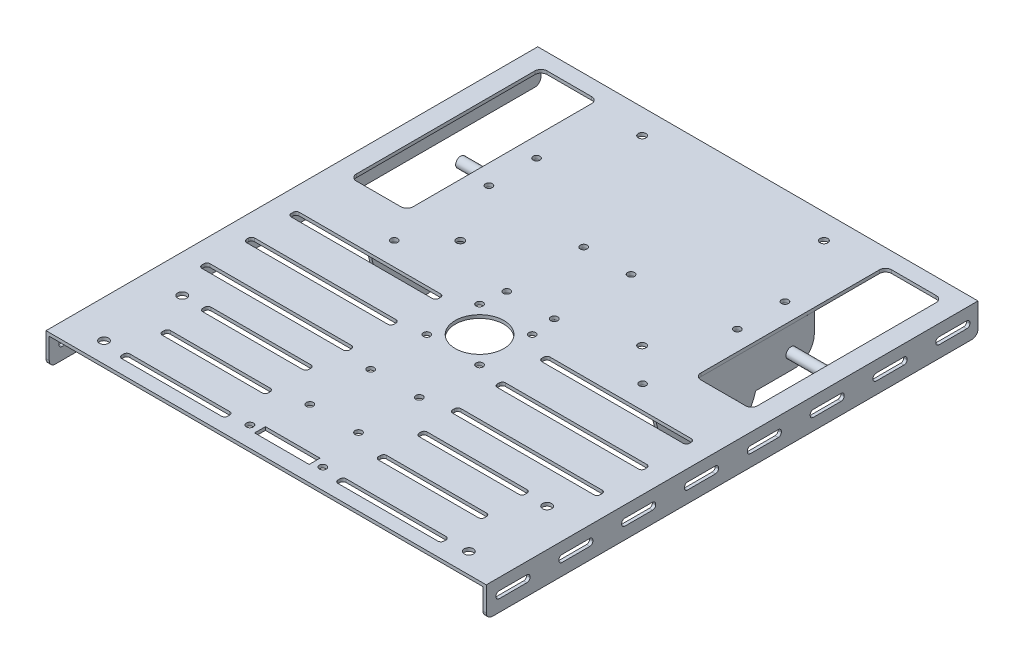
SolidWorks part; units mm, degrees
ref_plane "Front Plane" through (0, 0, 0) normal (0, 0, 1) x (1, 0, 0)
ref_plane "Top Plane" through (0, 0, 0) normal (0, 1, 0) x (1, 0, 0)
ref_plane "Right Plane" through (0, 0, 0) normal (1, 0, 0) x (0, 0, -1)
sketch "Sketch2" plane through (0, 0, 0) normal (0, 1, 0) x (1, 0, 0)
  line L7 (-172.2662, -88.2141) -> (41.7338, -88.2141)
  line L48 (-164.2662, 146.3841) -> (-136.2662, 146.3841)
  line L49 (-164.2662, 146.3841) -> (-164.2662, 52.2603)
  line L50 (-164.2662, 52.2603) -> (-136.2662, 52.2603)
  line L51 (-136.2662, 146.3841) -> (-136.2662, 52.2603)
  line L72 (41.7338, 154.3841) -> (-172.2662, 154.3841)
  line L75 (-65.2662, 154.3841) -> (-65.2662, -88.2141) construction
  line L76 (41.7338, -88.2141) -> (41.7338, 154.3841)
  line L77 (5.7338, 146.3841) -> (5.7338, 52.2603)
  line L78 (33.7338, 52.2603) -> (5.7338, 52.2603)
  line L79 (-172.2662, -88.2141) -> (-172.2662, 154.3841)
  line L80 (33.7338, 146.3841) -> (33.7338, 52.2603)
  line L81 (33.7338, 146.3841) -> (5.7338, 146.3841)
  point P2 (-150.2662, 146.3841)
  dimension "D1" = 8
  dimension "D3" = 8
  dimension "D6" = 107
  dimension "D9" = 28
extrude "Boss-Extrude1" add sketch "Sketch2" along normal blind 1.6
ref_plane "Plane3" through (-65.2662, 0, 0) normal (-1, 0, 0) x (0, 0, 1)
sketch "Sketch4" plane through (0, 0, 0) normal (0, -1, 0) x (1, 0, 0)
  line L5 (-172.2662, 15.9553) -> (41.7338, 15.9553) construction
  line L6 (-172.2662, -154.3841) -> (-172.2662, 88.2141) construction
  line L7 (41.7338, 88.2141) -> (41.7338, -154.3841) construction
  point P6 (-65.2662, 15.9553)
  line B0 (-136.2673, -111.2297) -> (-136.2673, -31.6718)
  line B1 (-136.2673, -111.2297) -> (-123.4267, -111.2297)
  line B2 (-136.2673, -31.6718) -> (-123.4299, -31.6718)
  line B3 (-72.7662, -37.9313) -> (-72.7662, -84.2325)
  line B4 (-72.7662, -37.9313) -> (-81.1807, -37.9313)
  line B5 (-72.7662, -84.2325) -> (-81.1807, -84.2325)
  line B6 (-118.4299, -36.6718) -> (-118.4299, -60.4336)
  line B7 (-118.4299, -60.4336) -> (-81.1807, -60.4336)
  line B8 (-81.1807, -60.4336) -> (-81.1807, -37.9313)
  line B9 (-81.1807, -84.2325) -> (-81.1807, -67.1203)
  line B10 (-81.1807, -67.1203) -> (-118.4267, -67.1203)
  line B11 (-118.4267, -67.1203) -> (-118.4267, -106.2297)
  arc B12 (-123.4299, -31.6718) -> (-118.4299, -36.6718) centre (-123.4299, -36.6718) cw
  arc B13 (-123.4267, -111.2297) -> (-118.4267, -106.2297) centre (-123.4267, -106.2297) ccw
  dimension "D1" = 7.5
sketch_block_instance "Block1-1"
sketch_block "Block1" parameters "D1"=5
extrude "Boss-Extrude3" add sketch "Sketch4" along normal blind 1.6129 separate body
sketch "Sketch6" plane through (-136.2673, 113.8349, 0) normal (1, 0, 0) x (0, -1, 0)
  line L1 (113.8349, 31.6718) -> (113.8349, 111.2297)
  line L7 (123.4041, 111.2297) -> (113.8349, 111.2297)
  line L8 (113.8349, 52.2603) -> (113.8349, 146.3841) construction
  line L10 (115.4478, 111.2297) -> (113.8349, 111.2297) construction
  line L11 (133.4041, 101.2297) -> (133.4041, 82.2567)
  line L13 (132.4365, 35.6062) -> (115.4478, 31.6718)
  line L14 (115.4478, 31.6718) -> (113.8349, 31.6718)
  circle A2 centre (133.4041, 71.8386) radius 1.27
  circle A4 centre (133.4041, 49.6644) radius 3
  circle A5 centre (125.8349, 99.7882) radius 2.55
  circle A6 centre (123.1933, 49.6644) radius 1.27
  circle A8 centre (143.6149, 49.6644) radius 1.27
  arc A10 (133.4041, 82.2567) -> (132.4365, 35.6062) centre (127.5185, 59.0435) cw
  arc A11 (133.4041, 101.2297) -> (123.4041, 111.2297) centre (123.4041, 101.2297) ccw
  line M25 (113.8349, 31.6718) -> (113.8349, 111.2297)
  line M26 (113.8349, 111.2297) -> (115.4478, 111.2297)
  line M27 (115.4478, 111.2297) -> (115.4478, 31.6718)
  line M28 (115.4478, 31.6718) -> (113.8349, 31.6718)
  dimension "D1" = 5.1
  dimension "D4" = 6
  dimension "D5" = 10
  dimension "D2" = 12
extrude "Boss-Extrude4" add sketch "Sketch6" along normal blind 1.6129 contours M28 M25 M26 M27 | M27 | A6 A2 A4 A8 region at (-136.2673, -0.8064, -71.4508) region at (-136.2673, -15.5641, -67.9069)
sketch "Sketch7" plane through (0, 0, 0) normal (0, -1, 0) x (1, 0, 0)
  line L0 (-172.2662, 88.2141) -> (41.7338, 88.2141) construction
  line L1 (-65.2662, -5.0799) -> (-65.2662, -29.0799)
  line L48 (-65.2662, -1159.7859) -> (-65.2662, 48840.2141) construction
  line L49 (41.7338, -154.3841) -> (-172.2662, -154.3841) construction
  line L50 (-65.2662, 80.4578) -> (-65.2662, 75.1009)
  line L51 (-65.2662, 80.4578) -> (-78.7298, 80.4578)
  line L52 (-65.2662, 75.1009) -> (-78.7298, 75.1009)
  line L53 (-78.7298, 80.4578) -> (-78.7298, 75.1009)
  circle A0 centre (-126.5406, -82.9719) radius 1.7
  circle A1 centre (-126.5406, -36.2597) radius 1.7
  circle A2 centre (-76.9734, -42.2194) radius 1.7
  circle A3 centre (-76.9734, -80.1262) radius 1.7
  circle A4 centre (-126.5406, -106.4792) radius 1.7
  circle A5 centre (-110.1162, -52.4299) radius 1.9
  circle A6 centre (-110.1162, -142.1299) radius 1.9
  circle A7 centre (-155.2662, 39.5701) radius 2.25
  circle A8 centre (-78.2662, -4.0799) radius 1.7
  circle A9 centre (-78.2662, -30.0799) radius 1.7
  arc A11 (-65.2662, -5.0799) -> (-65.2662, -29.0799) centre (-65.2662, -17.0799) ccw
  circle A12 centre (-83.2662, 78.2141) radius 1.7
  circle A13 centre (-77.2662, 24.6349) radius 1.7
  circle A14 centre (-77.2662, 54.6349) radius 1.7
  circle A15 centre (-155.2662, 78.2141) radius 2.25
  point P38 (-65.2662, -154.3841)
  dimension "D3" = 3.4
  dimension "D4" = 3.4
  dimension "D5" = 3.4
  dimension "D6" = 3.4
  dimension "D1" = 3.4
  dimension "D2" = 3.8
  dimension "D8" = 3.8
  dimension "D9" = 4.5
  dimension "D12" = 3.4
  dimension "D13" = 3.4
  dimension "D14" = 12
  dimension "D20" = 3.4
  dimension "D23" = 3.4
  dimension "D24" = 3.4
  dimension "D22" = 10
  dimension "D25" = 30
  dimension "D15" = 13
  dimension "D19" = 12
  dimension "D21" = 18
  dimension "D11" = 89.7
  dimension "D17" = 13
  dimension "D18" = 26
  dimension "D7" = 92
  dimension "D16" = 44.85
  dimension "D10" = 90
  dimension "D28" = 35.35
extrude "Cut-Extrude1" cut sketch "Sketch7" against normal blind 10 and the other way blind 10
mirror "Mirror1" about plane through (-65.2662, 0, 0) normal (-1, 0, 0) of bodies 157 158 103
mirror "Mirror2" about plane through (-65.2662, 0, 0) normal (-1, 0, 0) of "Cut-Extrude1"
sketch "Sketch9" plane through (-136.2662, 0, 0) normal (1, 0, 0) x (0, 0, -1)
  circle A0 centre (99.7882, -12) radius 2.5
extrude "Boss-Extrude6" add sketch "Sketch9" along normal blind 169 and the other way blind 21 separate body
sketch "Sketch11" plane through (0, 1.6, 0) normal (0, 1, 0) x (1, 0, 0)
  line L0 (-172.2662, 154.3841) -> (-172.2662, -88.2141)
  line L1 (-172.2662, 154.3841) -> (-173.8662, 154.3841)
  line L2 (-172.2662, -88.2141) -> (-173.8662, -88.2141)
  line L3 (-173.8662, 154.3841) -> (-173.8662, -88.2141)
  line L4 (41.7338, 154.3841) -> (41.7338, -88.2141)
  line L5 (41.7338, 154.3841) -> (43.3338, 154.3841)
  line L6 (41.7338, -88.2141) -> (43.3338, -88.2141)
  line L7 (43.3338, 154.3841) -> (43.3338, -88.2141)
  dimension "D1" = 1.6
  dimension "D2" = 1.6
extrude "Boss-Extrude7" add sketch "Sketch11" against normal blind 15
sketch "Sketch12" plane through (0, 1.6, 0) normal (0, 1, 0) x (1, 0, 0)
  line L12 (-65.2662, -1088.2141) -> (-65.2662, 48911.7859) construction
  line L13 (-173.8662, -88.2141) -> (43.3338, -88.2141) construction
  line L78 (-161.9933, 24.8362) -> (-92.2703, 24.8362)
  line L79 (-163.4933, 23.3362) -> (-163.4933, 22.3362)
  line L80 (-90.7703, 23.3362) -> (-90.7703, 22.3362)
  line L81 (-161.9933, 20.8362) -> (-92.2703, 20.8362)
  line L98 (-143.2458, -37.4749) -> (-93.977, -37.4749)
  line L99 (-144.7458, -38.9749) -> (-144.7458, -39.9749)
  line L100 (-92.477, -38.9749) -> (-92.477, -39.9749)
  line L101 (-143.2458, -41.4749) -> (-93.977, -41.4749)
  line L134 (-161.9933, -1.1638) -> (-92.2703, -1.1638)
  line L135 (-90.7703, 1.3362) -> (-90.7703, 0.3362)
  line L136 (-161.9933, 2.8362) -> (-92.2703, 2.8362)
  line L137 (-163.4933, 1.3362) -> (-163.4933, 0.3362)
  line L138 (-161.9933, -23.1638) -> (-92.2703, -23.1638)
  line L139 (-90.7703, -20.6638) -> (-90.7703, -21.6638)
  line L140 (-161.9933, -19.1638) -> (-92.2703, -19.1638)
  line L141 (-163.4933, -20.6638) -> (-163.4933, -21.6638)
  line L142 (-143.2458, -57.4749) -> (-93.977, -57.4749)
  line L143 (-144.7458, -58.9749) -> (-144.7458, -59.9749)
  line L144 (-92.477, -58.9749) -> (-92.477, -59.9749)
  line L145 (-143.2458, -61.4749) -> (-93.977, -61.4749)
  line L146 (-143.2458, -77.4749) -> (-93.977, -77.4749)
  line L147 (-144.7458, -78.9749) -> (-144.7458, -79.9749)
  line L148 (-92.477, -78.9749) -> (-92.477, -79.9749)
  line L149 (-143.2458, -81.4749) -> (-93.977, -81.4749)
  line L150 (12.7134, -81.4749) -> (-36.5554, -81.4749)
  line L151 (-38.0554, -78.9749) -> (-38.0554, -79.9749)
  line L152 (14.2134, -78.9749) -> (14.2134, -79.9749)
  line L153 (12.7134, -77.4749) -> (-36.5554, -77.4749)
  line L154 (12.7134, -61.4749) -> (-36.5554, -61.4749)
  line L155 (-38.0554, -58.9749) -> (-38.0554, -59.9749)
  line L156 (14.2134, -58.9749) -> (14.2134, -59.9749)
  line L157 (12.7134, -57.4749) -> (-36.5554, -57.4749)
  line L158 (32.9609, -20.6638) -> (32.9609, -21.6638)
  line L159 (31.4609, -19.1638) -> (-38.2621, -19.1638)
  line L160 (-39.7621, -20.6638) -> (-39.7621, -21.6638)
  line L161 (31.4609, -23.1638) -> (-38.2621, -23.1638)
  line L162 (32.9609, 1.3362) -> (32.9609, 0.3362)
  line L163 (31.4609, 2.8362) -> (-38.2621, 2.8362)
  line L164 (-39.7621, 1.3362) -> (-39.7621, 0.3362)
  line L165 (31.4609, -1.1638) -> (-38.2621, -1.1638)
  line L166 (12.7134, -41.4749) -> (-36.5554, -41.4749)
  line L167 (-38.0554, -38.9749) -> (-38.0554, -39.9749)
  line L168 (14.2134, -38.9749) -> (14.2134, -39.9749)
  line L169 (12.7134, -37.4749) -> (-36.5554, -37.4749)
  line L170 (31.4609, 20.8362) -> (-38.2621, 20.8362)
  line L171 (-39.7621, 23.3362) -> (-39.7621, 22.3362)
  line L172 (32.9609, 23.3362) -> (32.9609, 22.3362)
  line L173 (31.4609, 24.8362) -> (-38.2621, 24.8362)
  arc A0 (-92.2703, 24.8362) -> (-90.7703, 23.3362) centre (-92.2703, 23.3362) cw
  arc A1 (-90.7703, 22.3362) -> (-92.2703, 20.8362) centre (-92.2703, 22.3362) cw
  arc A2 (-163.4933, 22.3362) -> (-161.9933, 20.8362) centre (-161.9933, 22.3362) ccw
  arc A3 (-163.4933, 23.3362) -> (-161.9933, 24.8362) centre (-161.9933, 23.3362) cw
  arc A4 (-90.7703, 0.3362) -> (-92.2703, -1.1638) centre (-92.2703, 0.3362) cw
  arc A5 (-92.2703, 2.8362) -> (-90.7703, 1.3362) centre (-92.2703, 1.3362) cw
  arc A6 (-163.4933, 1.3362) -> (-161.9933, 2.8362) centre (-161.9933, 1.3362) cw
  arc A7 (-163.4933, 0.3362) -> (-161.9933, -1.1638) centre (-161.9933, 0.3362) ccw
  arc A8 (-90.7703, -21.6638) -> (-92.2703, -23.1638) centre (-92.2703, -21.6638) cw
  arc A9 (-92.2703, -19.1638) -> (-90.7703, -20.6638) centre (-92.2703, -20.6638) cw
  arc A10 (-163.4933, -20.6638) -> (-161.9933, -19.1638) centre (-161.9933, -20.6638) cw
  arc A11 (-163.4933, -21.6638) -> (-161.9933, -23.1638) centre (-161.9933, -21.6638) ccw
  arc A12 (-93.977, -37.4749) -> (-92.477, -38.9749) centre (-93.977, -38.9749) cw
  arc A13 (-92.477, -39.9749) -> (-93.977, -41.4749) centre (-93.977, -39.9749) cw
  arc A14 (-144.7458, -39.9749) -> (-143.2458, -41.4749) centre (-143.2458, -39.9749) ccw
  arc A15 (-144.7458, -38.9749) -> (-143.2458, -37.4749) centre (-143.2458, -38.9749) cw
  arc A32 (-93.977, -57.4749) -> (-92.477, -58.9749) centre (-93.977, -58.9749) cw
  arc A33 (-92.477, -59.9749) -> (-93.977, -61.4749) centre (-93.977, -59.9749) cw
  arc A34 (-144.7458, -59.9749) -> (-143.2458, -61.4749) centre (-143.2458, -59.9749) ccw
  arc A35 (-144.7458, -58.9749) -> (-143.2458, -57.4749) centre (-143.2458, -58.9749) cw
  arc A36 (-93.977, -77.4749) -> (-92.477, -78.9749) centre (-93.977, -78.9749) cw
  arc A37 (-92.477, -79.9749) -> (-93.977, -81.4749) centre (-93.977, -79.9749) cw
  arc A38 (-144.7458, -79.9749) -> (-143.2458, -81.4749) centre (-143.2458, -79.9749) ccw
  arc A39 (-144.7458, -78.9749) -> (-143.2458, -77.4749) centre (-143.2458, -78.9749) cw
  arc A40 (14.2134, -78.9749) -> (12.7134, -77.4749) centre (12.7134, -78.9749) ccw
  arc A41 (14.2134, -79.9749) -> (12.7134, -81.4749) centre (12.7134, -79.9749) cw
  arc A42 (-38.0554, -79.9749) -> (-36.5554, -81.4749) centre (-36.5554, -79.9749) ccw
  arc A43 (-36.5554, -77.4749) -> (-38.0554, -78.9749) centre (-36.5554, -78.9749) ccw
  arc A44 (14.2134, -58.9749) -> (12.7134, -57.4749) centre (12.7134, -58.9749) ccw
  arc A45 (14.2134, -59.9749) -> (12.7134, -61.4749) centre (12.7134, -59.9749) cw
  arc A46 (-38.0554, -59.9749) -> (-36.5554, -61.4749) centre (-36.5554, -59.9749) ccw
  arc A47 (-36.5554, -57.4749) -> (-38.0554, -58.9749) centre (-36.5554, -58.9749) ccw
  arc A48 (14.2134, -38.9749) -> (12.7134, -37.4749) centre (12.7134, -38.9749) ccw
  arc A49 (14.2134, -39.9749) -> (12.7134, -41.4749) centre (12.7134, -39.9749) cw
  arc A50 (-38.0554, -39.9749) -> (-36.5554, -41.4749) centre (-36.5554, -39.9749) ccw
  arc A51 (-36.5554, -37.4749) -> (-38.0554, -38.9749) centre (-36.5554, -38.9749) ccw
  arc A52 (32.9609, -21.6638) -> (31.4609, -23.1638) centre (31.4609, -21.6638) cw
  arc A53 (32.9609, -20.6638) -> (31.4609, -19.1638) centre (31.4609, -20.6638) ccw
  arc A54 (-38.2621, -19.1638) -> (-39.7621, -20.6638) centre (-38.2621, -20.6638) ccw
  arc A55 (-39.7621, -21.6638) -> (-38.2621, -23.1638) centre (-38.2621, -21.6638) ccw
  arc A56 (32.9609, 0.3362) -> (31.4609, -1.1638) centre (31.4609, 0.3362) cw
  arc A57 (32.9609, 1.3362) -> (31.4609, 2.8362) centre (31.4609, 1.3362) ccw
  arc A58 (-38.2621, 2.8362) -> (-39.7621, 1.3362) centre (-38.2621, 1.3362) ccw
  arc A59 (-39.7621, 0.3362) -> (-38.2621, -1.1638) centre (-38.2621, 0.3362) ccw
  arc A60 (32.9609, 23.3362) -> (31.4609, 24.8362) centre (31.4609, 23.3362) ccw
  arc A61 (32.9609, 22.3362) -> (31.4609, 20.8362) centre (31.4609, 22.3362) cw
  arc A62 (-39.7621, 22.3362) -> (-38.2621, 20.8362) centre (-38.2621, 22.3362) ccw
  arc A63 (-38.2621, 24.8362) -> (-39.7621, 23.3362) centre (-38.2621, 23.3362) ccw
  point P41 (-65.2662, -88.2141)
  point P42 (-92.477, -37.4749)
  point P45 (-92.477, -41.4749)
  point P48 (-144.7458, -41.4749)
  point P51 (-144.7458, -37.4749)
  point P55 (-90.7703, 24.8362)
  point P58 (-90.7703, 20.8362)
  point P61 (-163.4933, 20.8362)
  point P64 (-163.4933, 24.8362)
  point P157 (32.9609, 24.8362)
  point P158 (32.9609, 20.8362)
  point P159 (-39.7621, 20.8362)
  point P160 (-39.7621, 24.8362)
  point P161 (14.2134, -37.4749)
  point P162 (14.2134, -41.4749)
  point P163 (-38.0554, -41.4749)
  point P164 (-38.0554, -37.4749)
  dimension "D1" = 1.5
  dimension "D3" = 1.5
  dimension "D2" = 3
extrude "Cut-Extrude2" cut sketch "Sketch12" against normal blind 8
sketch "Sketch13" plane through (-173.8662, 0, 0) normal (-1, 0, 0) x (0, 0, 1)
  line L0 (-148.8578, -4.1114) -> (-135.1046, -4.1114)
  line L1 (-150.3578, -5.6114) -> (-150.3578, -6.0114)
  line L2 (-133.6046, -5.6114) -> (-133.6046, -6.0114)
  line L3 (-148.8578, -7.5114) -> (-135.1046, -7.5114)
  line L4 (-102.6046, -5.6114) -> (-102.6046, -6.0114)
  line L5 (-117.8578, -7.5114) -> (-104.1046, -7.5114)
  line L6 (-119.3578, -5.6114) -> (-119.3578, -6.0114)
  line L7 (-117.8578, -4.1114) -> (-104.1046, -4.1114)
  line L8 (-71.6046, -5.6114) -> (-71.6046, -6.0114)
  line L9 (-86.8578, -7.5114) -> (-73.1046, -7.5114)
  line L10 (-88.3578, -5.6114) -> (-88.3578, -6.0114)
  line L11 (-86.8578, -4.1114) -> (-73.1046, -4.1114)
  line L12 (-40.6046, -5.6114) -> (-40.6046, -6.0114)
  line L13 (-55.8578, -7.5114) -> (-42.1046, -7.5114)
  line L14 (-57.3578, -5.6114) -> (-57.3578, -6.0114)
  line L15 (-55.8578, -4.1114) -> (-42.1046, -4.1114)
  line L16 (-9.6046, -5.6114) -> (-9.6046, -6.0114)
  line L17 (-24.8578, -7.5114) -> (-11.1046, -7.5114)
  line L18 (-26.3578, -5.6114) -> (-26.3578, -6.0114)
  line L19 (-24.8578, -4.1114) -> (-11.1046, -4.1114)
  line L20 (21.3954, -5.6114) -> (21.3954, -6.0114)
  line L21 (6.1422, -7.5114) -> (19.8954, -7.5114)
  line L22 (4.6422, -5.6114) -> (4.6422, -6.0114)
  line L23 (6.1422, -4.1114) -> (19.8954, -4.1114)
  line L24 (52.3954, -5.6114) -> (52.3954, -6.0114)
  line L25 (37.1422, -7.5114) -> (50.8954, -7.5114)
  line L26 (35.6422, -5.6114) -> (35.6422, -6.0114)
  line L27 (37.1422, -4.1114) -> (50.8954, -4.1114)
  line L28 (83.3954, -5.6114) -> (83.3954, -6.0114)
  line L29 (68.1422, -7.5114) -> (81.8954, -7.5114)
  line L30 (66.6422, -5.6114) -> (66.6422, -6.0114)
  line L31 (68.1422, -4.1114) -> (81.8954, -4.1114)
  arc A0 (-150.3578, -6.0114) -> (-148.8578, -7.5114) centre (-148.8578, -6.0114) ccw
  arc A1 (-133.6046, -6.0114) -> (-135.1046, -7.5114) centre (-135.1046, -6.0114) cw
  arc A2 (-135.1046, -4.1114) -> (-133.6046, -5.6114) centre (-135.1046, -5.6114) cw
  arc A3 (-150.3578, -5.6114) -> (-148.8578, -4.1114) centre (-148.8578, -5.6114) cw
  arc A4 (-102.6046, -6.0114) -> (-104.1046, -7.5114) centre (-104.1046, -6.0114) cw
  arc A5 (-119.3578, -6.0114) -> (-117.8578, -7.5114) centre (-117.8578, -6.0114) ccw
  arc A6 (-119.3578, -5.6114) -> (-117.8578, -4.1114) centre (-117.8578, -5.6114) cw
  arc A7 (-104.1046, -4.1114) -> (-102.6046, -5.6114) centre (-104.1046, -5.6114) cw
  arc A8 (-71.6046, -6.0114) -> (-73.1046, -7.5114) centre (-73.1046, -6.0114) cw
  arc A9 (-88.3578, -6.0114) -> (-86.8578, -7.5114) centre (-86.8578, -6.0114) ccw
  arc A10 (-88.3578, -5.6114) -> (-86.8578, -4.1114) centre (-86.8578, -5.6114) cw
  arc A11 (-73.1046, -4.1114) -> (-71.6046, -5.6114) centre (-73.1046, -5.6114) cw
  arc A12 (-40.6046, -6.0114) -> (-42.1046, -7.5114) centre (-42.1046, -6.0114) cw
  arc A13 (-57.3578, -6.0114) -> (-55.8578, -7.5114) centre (-55.8578, -6.0114) ccw
  arc A14 (-57.3578, -5.6114) -> (-55.8578, -4.1114) centre (-55.8578, -5.6114) cw
  arc A15 (-42.1046, -4.1114) -> (-40.6046, -5.6114) centre (-42.1046, -5.6114) cw
  arc A16 (-9.6046, -6.0114) -> (-11.1046, -7.5114) centre (-11.1046, -6.0114) cw
  arc A17 (-26.3578, -6.0114) -> (-24.8578, -7.5114) centre (-24.8578, -6.0114) ccw
  arc A18 (-26.3578, -5.6114) -> (-24.8578, -4.1114) centre (-24.8578, -5.6114) cw
  arc A19 (-11.1046, -4.1114) -> (-9.6046, -5.6114) centre (-11.1046, -5.6114) cw
  arc A20 (21.3954, -6.0114) -> (19.8954, -7.5114) centre (19.8954, -6.0114) cw
  arc A21 (4.6422, -6.0114) -> (6.1422, -7.5114) centre (6.1422, -6.0114) ccw
  arc A22 (4.6422, -5.6114) -> (6.1422, -4.1114) centre (6.1422, -5.6114) cw
  arc A23 (19.8954, -4.1114) -> (21.3954, -5.6114) centre (19.8954, -5.6114) cw
  arc A24 (52.3954, -6.0114) -> (50.8954, -7.5114) centre (50.8954, -6.0114) cw
  arc A25 (35.6422, -6.0114) -> (37.1422, -7.5114) centre (37.1422, -6.0114) ccw
  arc A26 (35.6422, -5.6114) -> (37.1422, -4.1114) centre (37.1422, -5.6114) cw
  arc A27 (50.8954, -4.1114) -> (52.3954, -5.6114) centre (50.8954, -5.6114) cw
  arc A28 (83.3954, -6.0114) -> (81.8954, -7.5114) centre (81.8954, -6.0114) cw
  arc A29 (66.6422, -6.0114) -> (68.1422, -7.5114) centre (68.1422, -6.0114) ccw
  arc A30 (66.6422, -5.6114) -> (68.1422, -4.1114) centre (68.1422, -5.6114) cw
  arc A31 (81.8954, -4.1114) -> (83.3954, -5.6114) centre (81.8954, -5.6114) cw
  dimension "D1" = 1.5
  dimension "D2" = 8
extrude "Cut-Extrude3" cut sketch "Sketch13" against normal blind 222
fillet "Fillet1" radius 3 12 edges at (-173.0662, -13.4, 88.2141) (-173.0662, -13.4, -154.3841) (42.5338, -13.4, -154.3841) (42.5338, -13.4, 88.2141) (-136.2662, 0.8, -52.2603) (-164.2662, 0.8, -146.3841) (-164.2662, 0.8, -52.2603) (-136.2662, 0.8, -146.3841) (33.7338, 0.8, -146.3841) (5.7338, 0.8, -146.3841) (33.7338, 0.8, -52.2603) (5.7338, 0.8, -52.2603)
equation "\"hardboard_width\"= 3.175"
equation "\"D1@Boss-Extrude1\"=\"hardboard_width\""
equation "\"steel_24g_thickness\"= 0.5"
equation "\"m3_clearance_hole\"= 3.4"
equation "\"D3@Sketch7\"=\"m3_clearance_hole\""
equation "\"D4@Sketch7\"=\"m3_clearance_hole\""
equation "\"D5@Sketch7\"=\"m3_clearance_hole\""
equation "\"D6@Sketch7\"=\"m3_clearance_hole\""
equation "\"steel_16g_thickness\"=1.6129"
equation "\"D1@Boss-Extrude3\"=\"steel_16g_thickness\""
equation "\"D1@Boss-Extrude4\"=\"steel_16g_thickness\""
equation "\"D1@Sketch7\"=\"m3_clearance_hole\""
equation "\"D12@Sketch7\"=\"m3_clearance_hole\""
equation "\"D20@Sketch7\"=\"m3_clearance_hole\""
equation "\"D23@Sketch7\"=\"m3_clearance_hole\""
equation "\"D24@Sketch7\"=\"m3_clearance_hole\""
equation "\"D13@Sketch7\"=\"m3_clearance_hole\""
equation "\"D28@Sketch7\"=80.2-44.85"
